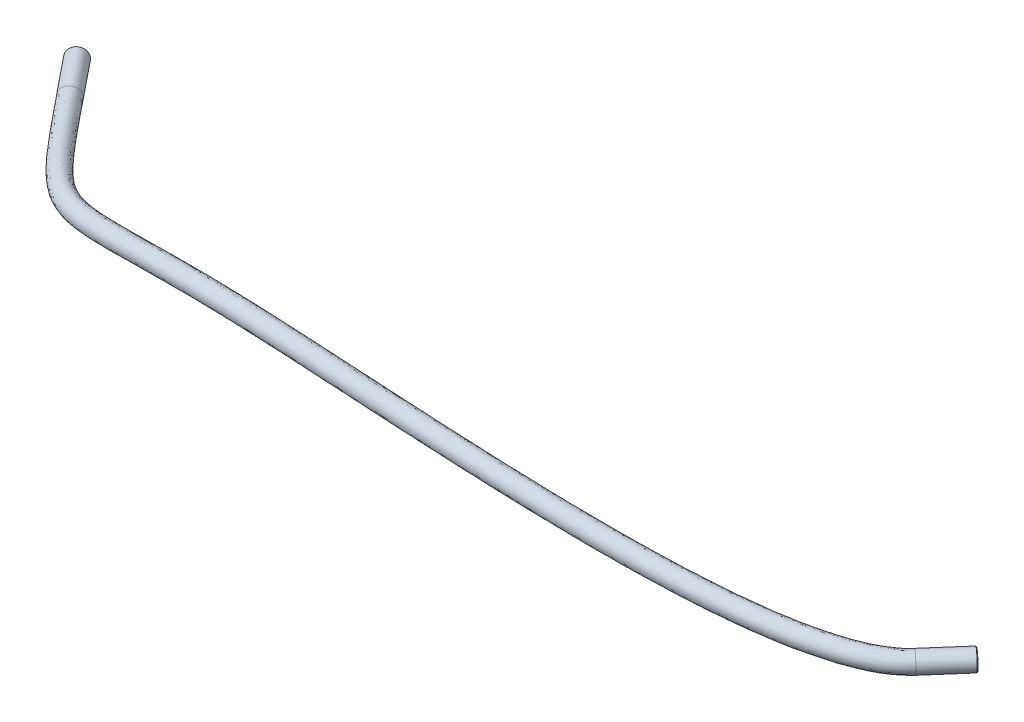
SolidWorks part; units mm, degrees
ref_plane "Front Plane" through (0, 0, 0) normal (0, 0, 1) x (1, 0, 0)
ref_plane "Top Plane" through (0, 0, 0) normal (0, 1, 0) x (1, 0, 0)
ref_plane "Right Plane" through (0, 0, 0) normal (1, 0, 0) x (0, 0, -1)
sketch3d "3DSketch1"
  line L0 (74.6041, -99.6875, 35.7814) -> (80.6644, -99.6875, 28.8595)
  line L1 (-122.4682, -99.5875, 13.9938) -> (-116.0543, -99.5875, 21.9249)
  spline S0 degree 3 poles (-116.0543, -99.5875, 21.9249) (-94.7613, -99.5875, 48.2549) (-106.3723, -99.6375, 35.0332) (59.8692, -99.6875, 52.6113) (74.6041, -99.6875, 35.7814) knots 0 0 0 0 0.504003 1 1 1 1
sketch "Sketch1" plane through (16.022, 0, -18.2998) normal (-0.6587, 0, 0.7524) x (0.7524, 0, 0.6587)
  circle A0 centre (79.701, -99.6875) radius 2
  circle A1 centre (79.701, -99.6875) radius 1.3
  circle A3 centre (79.701, -99.6875) radius 3.5524 construction
  dimension "D1" = 2.6
  dimension "D2" = 4
sweep "Sweep2" add profiles "Sketch1" path "3DSketch1"
chamfer "Chamfer1" distance 0.127 angle 45 4 edges at (-124.0229, -99.5438, 15.2511) (-123.4787, -99.5591, 14.8111) (82.1692, -99.6875, 30.177) (81.6425, -99.6875, 29.7159)
